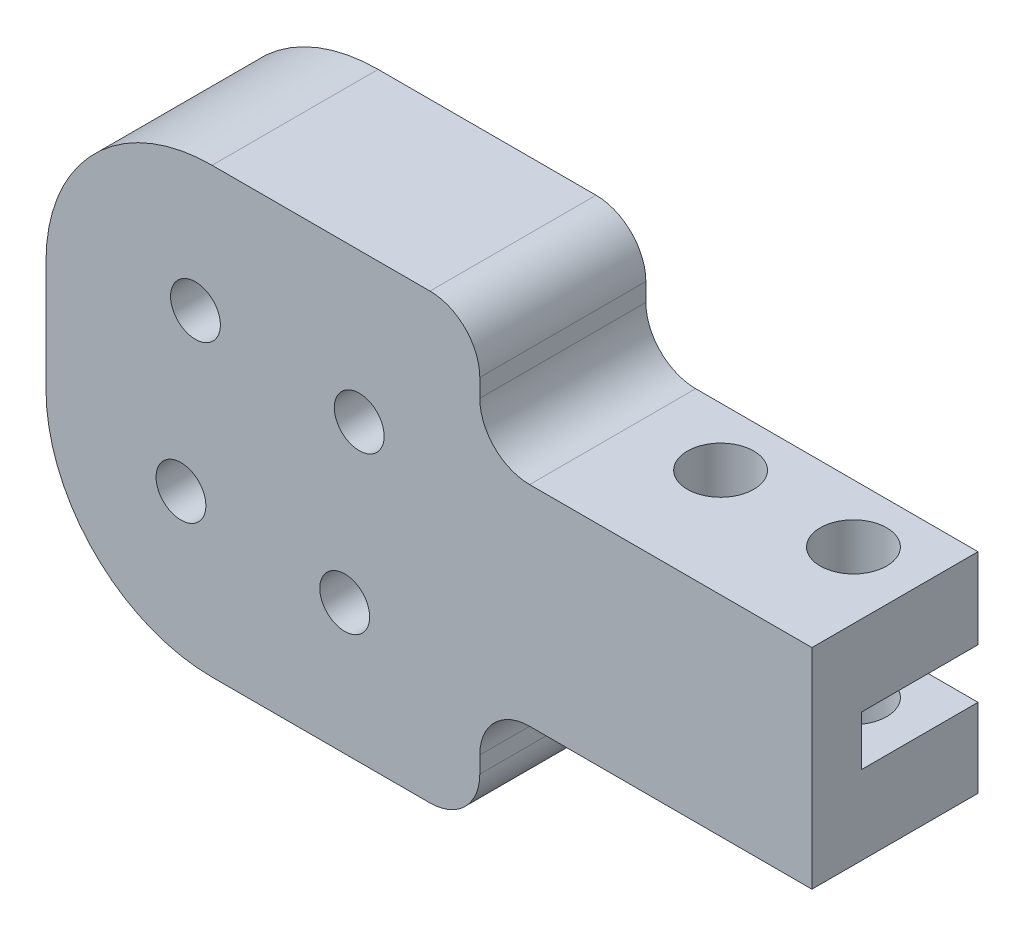
SolidWorks part; units mm, degrees
ref_plane "Plan de face" through (0, 0, 0) normal (0, 0, 1) x (1, 0, 0)
ref_plane "Plan de dessus" through (0, 0, 0) normal (0, 1, 0) x (1, 0, 0)
ref_plane "Plan de droite" through (0, 0, 0) normal (1, 0, 0) x (0, 0, -1)
sketch "Esquisse1" plane through (0, 0, 0) normal (0, 0, 1) x (1, 0, 0)
  circle A0 centre (-18.394, 17.8631) radius 50
  dimension "D1" = 100
extrude "Boss.-Extru.1" add sketch "Esquisse1" along normal blind 10
sketch "Esquisse2" plane through (0, 0, 0) normal (0, 0, -1) x (-1, 0, 0)
  circle A0 centre (18.394, 17.8631) radius 10
  circle A4 centre (18.394, 17.8631) radius 50 construction
  dimension "D1" = 20
  dimension "D2" = 40
extrude "Enlèv. mat.-Extru.1" cut sketch "Esquisse2" against normal blind 7
sketch "Esquisse4" plane through (0, 0, 0) normal (0, 0, -1) x (-1, 0, 0)
  line L1 (13.6656, 19.3631) -> (-38.5885, 19.3631)
  line L2 (13.6656, 19.3631) -> (13.6656, 16.3631)
  line L3 (13.6656, 16.3631) -> (-38.5885, 16.3631)
  line L4 (-38.5885, 19.3631) -> (-38.5885, 16.3631)
  circle A1 centre (18.394, 17.8631) radius 50 construction
  dimension "D1" = 3
  dimension "D2" = 1.5
extrude "Enlèv. mat.-Extru.2" cut sketch "Esquisse4" against normal blind 7
sketch "Esquisse6" plane through (0, 0, 0) normal (0, 0, -1) x (-1, 0, 0)
  line L1 (-31.8143, 71.3621) -> (77.2564, 71.3621)
  line L2 (-31.8143, 71.3621) -> (-31.8143, 31.3086)
  line L3 (-31.8143, 31.3086) -> (77.2564, 31.3086)
  line L4 (77.2564, 71.3621) -> (77.2564, 31.3086)
extrude "Enlèv. mat.-Extru.3" cut sketch "Esquisse6" against normal blind 10
sketch "Esquisse8" plane through (0, 0, 0) normal (0, 0, -1) x (-1, 0, 0)
  line L1 (75.3431, -32.0235) -> (31.8877, -32.0235)
  line L2 (75.3431, -32.0235) -> (75.3431, 40.996)
  line L3 (75.3431, 40.996) -> (31.8877, 40.996)
  line L4 (31.8877, -32.0235) -> (31.8877, 40.996)
extrude "Enlèv. mat.-Extru.4" cut sketch "Esquisse8" against normal blind 10
sketch "Esquisse9" plane through (0, 0, 0) normal (0, 0, -1) x (-1, 0, 0)
  line L1 (41.6051, -36.7211) -> (-41.6048, -36.7211)
  line L2 (41.6051, -36.7211) -> (41.6051, 4.6153)
  line L3 (41.6051, 4.6153) -> (-41.6048, 4.6153)
  line L4 (-41.6048, -36.7211) -> (-41.6048, 4.6153)
extrude "Enlèv. mat.-Extru.5" cut sketch "Esquisse9" against normal blind 10
sketch "Esquisse10" plane through (0, 0, 0) normal (0, 0, -1) x (-1, 0, 0)
  line L1 (-14.2326, 40.0528) -> (-46.2301, 40.0528)
  line L2 (-14.2326, 40.0528) -> (-14.2326, -10.5706)
  line L3 (-14.2326, -10.5706) -> (-46.2301, -10.5706)
  line L4 (-46.2301, 40.0528) -> (-46.2301, -10.5706)
  line L6 (-14.2326, 12.9026) -> (-14.2326, 12.3073)
  line L8 (-10.3832, 12.9026) -> (-10.3832, 12.3073)
extrude "Enlèv. mat.-Extru.6" cut sketch "Esquisse10" against normal blind 10 contours L2 L3 L4 L1
sketch "Esquisse11" plane through (0, 0, 7) normal (0, 0, -1) x (-1, 0, 0)
  line L0 (31.8877, 31.3086) -> (31.8877, 4.6153) construction
  circle A0 centre (22.8877, 23.2303) radius 1.5
  arc A1 (8.5071, 16.3631) -> (8.5071, 19.3631) centre (18.394, 17.8631) ccw construction
  dimension "D1" = 7
  dimension "D2" = 3
  dimension "D3" = 9
extrude "Enlèv. mat.-Extru.7" cut sketch "Esquisse11" against normal blind 10
fillet "Congé1" radius 10 2 edges at (-31.8877, 31.3086, 5) (-31.8877, 4.6153, 5)
sketch "Esquisse16" plane through (0, 0, 0) normal (0, 0, -1) x (-1, 0, 0)
  line L1 (-14.2326, 4.6153) -> (5.7674, 4.6153)
  line L2 (-14.2326, 4.6153) -> (-14.2326, 11.6153)
  line L3 (-14.2326, 11.6153) -> (5.7674, 11.6153)
  line L4 (5.7674, 4.6153) -> (5.7674, 11.6153)
extrude "Enlèv. mat.-Extru.11" cut sketch "Esquisse16" against normal blind 10
fillet "Congé2" radius 3 2 edges at (-5.7674, 4.6153, 5) (-5.7674, 11.6153, 5)
pattern_circular "Répétition circulaire1" count 4 over 360 about axis through (-18.394, 17.8631, 7) along (0, 0, -1) of "Enlèv. mat.-Extru.7"
sketch "Esquisse17" plane through (0, 0, 0) normal (0, 0, -1) x (-1, 0, 0)
  line L1 (-14.2326, 31.3086) -> (5.7674, 31.3086)
  line L2 (-14.2326, 31.3086) -> (-14.2326, 24.2181)
  line L3 (-14.2326, 24.2181) -> (5.7674, 24.2181)
  line L4 (5.7674, 31.3086) -> (5.7674, 24.2181)
extrude "Enlèv. mat.-Extru.12" cut sketch "Esquisse17" against normal blind 10
fillet "Congé3" radius 3 2 edges at (-5.7674, 24.2181, 5) (-5.7674, 31.3086, 5)
sketch "Esquisse19" plane through (0, 11.6153, 0) normal (0, -1, 0) x (1, 0, 0)
  line L0 (14.2326, 10) -> (14.2326, 0) construction
  line L1 (-2.7674, 0) -> (14.2326, 0) construction
  circle A0 centre (10.2326, 3.5) radius 2
  circle A1 centre (2.2326, 3.5) radius 2
  dimension "D1" = 4
  dimension "D2" = 3.5
  dimension "D3" = 8
  dimension "D4" = 3.5
extrude "Enlèv. mat.-Extru.13" cut sketch "Esquisse19" against normal blind 20 contours A0
extrude "Enlèv. mat.-Extru.14" cut sketch "Esquisse19<3>" against normal blind 20
sketch "Esquisse19<3>" plane through (0, 11.6153, 0) normal (0, -1, 0) x (1, 0, 0) same geometry as "Esquisse19"
